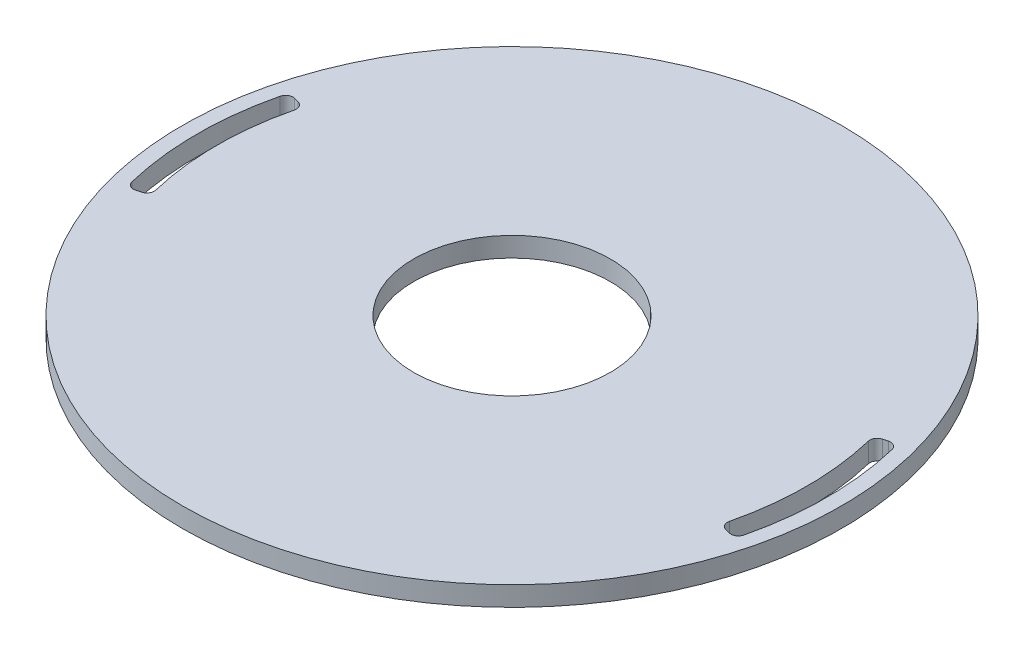
SolidWorks part; units mm, degrees
material "ABS"
ref_plane "Front Plane" through (0, 0, 0) normal (0, 0, 1) x (1, 0, 0)
ref_plane "Top Plane" through (0, 0, 0) normal (0, 1, 0) x (1, 0, 0)
ref_plane "Right Plane" through (0, 0, 0) normal (1, 0, 0) x (0, 0, -1)
sketch "Эскиз1" plane through (0, 0, 0) normal (0, 1, 0) x (1, 0, 0)
  circle A0 centre (0, 0) radius 33.5
  circle A1 centre (0, 0) radius 10
  dimension "D1" = 20
  dimension "D2" = 67
extrude "Бобышка-Вытянуть1" add sketch "Эскиз1" along normal blind 2
sketch "Эскиз2" plane through (0, 0, 0) normal (0, -1, 0) x (1, 0, 0)
  line L0 (0, 0) -> (0, 25) construction
  line L2 (0, 0) -> (25, 0) construction
  line L3 (0, 0) -> (-25, 0) construction
  line L4 (0, -23.75) -> (0, -25) construction
  circle A0 centre (0, 25) radius 1.25
  circle A1 centre (-25, 0) radius 1.25
  circle A2 centre (25, 0) radius 1.25
  circle A3 centre (0, -25) radius 1.25
  dimension "D1" = 2.5
  dimension "D2" = 25
extrude "Бобышка-Вытянуть2" add sketch "Эскиз2" along normal blind 2.5
sketch "Эскиз3" plane through (0, 2, 0) normal (0, 1, 0) x (1, 0, 0)
  line L0 (0, 0) -> (-32, 0) construction
  line L1 (0, 0) -> (0, 15.5268) construction
  line L2 (-29.6934, 7.9563) -> (-30.1765, 8.0858)
  line L3 (-29.6934, -7.9563) -> (-30.1765, -8.0858)
  line L4 (29.6934, -7.9563) -> (30.1765, -8.0858)
  line L5 (29.6934, 7.9563) -> (30.1765, 8.0858)
  arc A0 (-31.0995, 7.538) -> (-31.0995, -7.538) centre (0, 0) ccw
  arc A1 (-29.1585, 7.0555) -> (-29.1585, -7.0555) centre (0, 0) ccw
  arc A2 (-30.1765, -8.0858) -> (-31.0995, -7.538) centre (-30.3706, -7.3613) cw
  arc A3 (-29.6934, -7.9563) -> (-29.1585, -7.0555) centre (-29.8875, -7.2319) ccw
  arc A4 (-31.0995, 7.538) -> (-30.1765, 8.0858) centre (-30.3706, 7.3613) cw
  arc A5 (-29.6934, 7.9563) -> (-29.1585, 7.0555) centre (-29.8875, 7.2319) cw
  arc A6 (29.6934, 7.9563) -> (29.1585, 7.0555) centre (29.8875, 7.2319) ccw
  arc A7 (31.0995, 7.538) -> (30.1765, 8.0858) centre (30.3706, 7.3613) ccw
  arc A8 (29.6934, -7.9563) -> (29.1585, -7.0555) centre (29.8875, -7.2319) cw
  arc A9 (30.1765, -8.0858) -> (31.0995, -7.538) centre (30.3706, -7.3613) ccw
  arc A10 (29.1585, 7.0555) -> (29.1585, -7.0555) centre (0, 0) cw
  arc A11 (31.0995, 7.538) -> (31.0995, -7.538) centre (0, 0) cw
  circle A12 centre (0, 0) radius 33.5 construction
  point P9 (-30.9096, -8.2822)
  point P14 (-30.9096, 8.2822)
  point P30 (30.9096, 8.2822)
  point P31 (30.9096, -8.2822)
  dimension "D1" = 0.75
  dimension "D2" = 32
  dimension "D3" = 30
  dimension "D4" = 29.1585
extrude "Вырез-Вытянуть1" cut sketch "Эскиз3" against normal up to surface (2 mm away) up to face at (0, 0, -23.75)
sketch "Эскиз4" plane through (0, 0, 0) normal (0, -1, 0) x (1, 0, 0)
  circle A0 centre (0, 0) radius 19
  circle A1 centre (0, 0) radius 20.5
  dimension "D1" = 38
  dimension "D2" = 41
extrude "Бобышка-Вытянуть3" add sketch "Эскиз4" along normal blind 4
sketch "Эскиз5" plane through (0, 0, 0) normal (0, -1, 0) x (1, 0, 0)
  line L0 (0, 0) -> (0, 14.5) construction
  circle A0 centre (0, 14.5) radius 1.25
  circle A1 centre (14.5, 0) radius 1.25
  circle A2 centre (0, -14.5) radius 1.25
  circle A3 centre (-14.5, 0) radius 1.25
  circle A4 centre (0, 0) radius 10 construction
  point P13 (0, 0)
  dimension "D1" = 4
  dimension "D2" = 2.5
  dimension "D3" = 14.5
extrude "Бобышка-Вытянуть4" add sketch "Эскиз5" along normal up to surface (2.5 mm away) up to face at (0, -2.5, 23.75)
